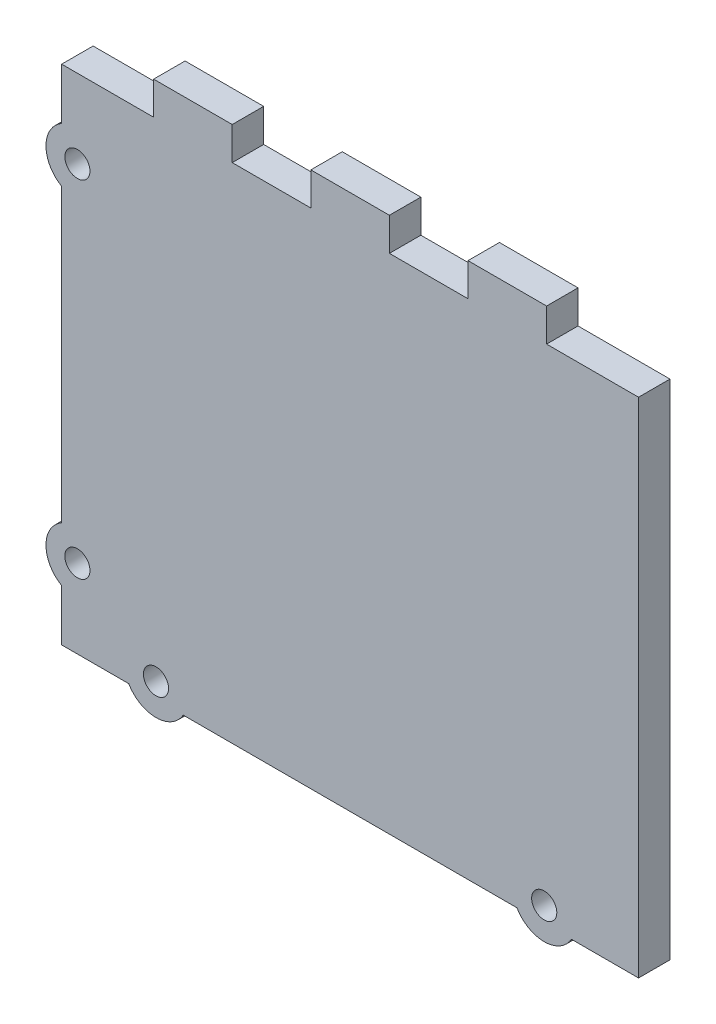
SolidWorks part; units mm, degrees
ref_plane "Front Plane" through (0, 0, 0) normal (0, 0, 1) x (1, 0, 0)
ref_plane "Top Plane" through (0, 0, 0) normal (0, 1, 0) x (1, 0, 0)
ref_plane "Right Plane" through (0, 0, 0) normal (1, 0, 0) x (0, 0, -1)
sketch "Sketch1" plane through (0, 0, 0) normal (0, 0, 1) x (1, 0, 0)
  line L0 (-23, -34.2) -> (-36.4, -34.2) construction
  line L2 (-36.5, 29.8) -> (-36.5, -34.2)
  line L3 (-36.5, -34.2) -> (36.9, -34.2)
  line L4 (36.9, 29.8) -> (36.9, -34.2)
  line L5 (-36.5, 29.8) -> (36.9, 29.8)
  line L7 (-36.5, -17) -> (-36.5, 16.6) construction
  point P0 (0, 0)
extrude "Boss-Extrude1" add sketch "Sketch1" along normal blind 4
sketch "Sketch2" plane through (0, 0, 4) normal (0, 0, 1) x (1, 0, 0)
  line L0 (-36.5, -34.2) -> (36.9, -34.2) construction
  line L1 (26.5, -34.2) -> (23.3, -34.2) construction
  line L2 (-36.5, 29.8) -> (-36.5, -34.2) construction
  line L4 (-32.5, 16.6) -> (-36.5, 16.6) construction
  line L5 (-36.5, 16.3359) -> (-36.5, 23.2641)
  line L6 (28.3665, -34.2) -> (21.4335, -34.2)
  circle A0 centre (24.9, -32.2042) radius 1.6
  arc A1 (28.3665, -34.2) -> (21.4335, -34.2) centre (24.9, -32.2042) cw
  circle A2 centre (-34.5, 19.8) radius 1.6
  arc A3 (-36.5, 16.3359) -> (-36.5, 23.2641) centre (-34.5, 19.8) cw
  point P9 (24.9, -34.2)
  line M6 (-36.5, 29.8) -> (-36.5, -34.2)
  line M7 (-36.5, -34.2) -> (36.9, -34.2)
  dimension "D1" = 3.2
  dimension "D2" = 4
  dimension "D4" = 3.2
  dimension "D6" = 4
  dimension "D7" = 3.2
  dimension "D3" = 1.9958
  dimension "D5" = 2
extrude "Boss-Extrude2" add sketch "Sketch2" against normal blind 4 contours A1 M7 region at (24.9, -35.0219, 4)
extrude "Cut-Extrude1" cut sketch "Sketch2<3>" against normal blind 4 contours A0 region at (24.9, -32.2042, 4)
sketch "Sketch2<3>" plane through (0, 0, 4) normal (0, 0, 1) x (1, 0, 0) same geometry as "Sketch2"
ref_plane "Plane1" through (0.2, 0, 0) normal (1, 0, 0) x (0, 0, -1)
mirror "Mirror1" about plane through (0.2, 0, 0) normal (1, 0, 0) of "Cut-Extrude1", "Boss-Extrude2"
ref_plane "Plane2" through (0, -2.2, 0) normal (0, -1, 0) x (-1, 0, 0)
extrude "Boss-Extrude3" add sketch "Sketch2<4>" against normal blind 4 contours A3 M6 region at (-37.3201, 19.8, 4)
sketch "Sketch2<4>" plane through (0, 0, 4) normal (0, 0, 1) x (1, 0, 0) same geometry as "Sketch2"
extrude "Cut-Extrude2" cut sketch "Sketch2<5>" against normal blind 4 contours A2 region at (-34.5, 19.8, 4)
sketch "Sketch2<5>" plane through (0, 0, 4) normal (0, 0, 1) x (1, 0, 0) same geometry as "Sketch2"
mirror "Mirror3" about plane through (0, -2.2, 0) normal (0, -1, 0) of "Boss-Extrude3", "Cut-Extrude2"
sketch "Sketch3" plane through (0, 0, 0) normal (0, 0, -1) x (-1, 0, 0)
  line L1 (-25.2, 29.5) -> (-15.2, 29.5)
  line L2 (-25.2, 29.5) -> (-25.2, 34)
  line L3 (-25.2, 34) -> (-15.2, 34)
  line L4 (-15.2, 29.5) -> (-15.2, 34)
  line L5 (-36.9, -34.2) -> (-36.9, 29.8) construction
  line L6 (4.8, 29.5) -> (4.8, 34)
  line L7 (-5.2, 34) -> (4.8, 34)
  line L8 (-5.2, 29.5) -> (-5.2, 34)
  line L9 (-5.2, 29.5) -> (4.8, 29.5)
  line L10 (24.8, 29.5) -> (24.8, 34)
  line L11 (14.8, 34) -> (24.8, 34)
  line L12 (14.8, 29.5) -> (14.8, 34)
  line L13 (14.8, 29.5) -> (24.8, 29.5)
  line L15 (-36.9, 29.8) -> (36.5, 29.8) construction
  dimension "D1" = 11.7
  dimension "D2" = 10
  dimension "D3" = 4.5
  dimension "D5" = 4.2
  dimension "D4" = 3
extrude "Boss-Extrude4" add sketch "Sketch3" against normal blind 4 separate body
combine bodies "Combine1" operation type add bodies to combine 109 108 110 111
